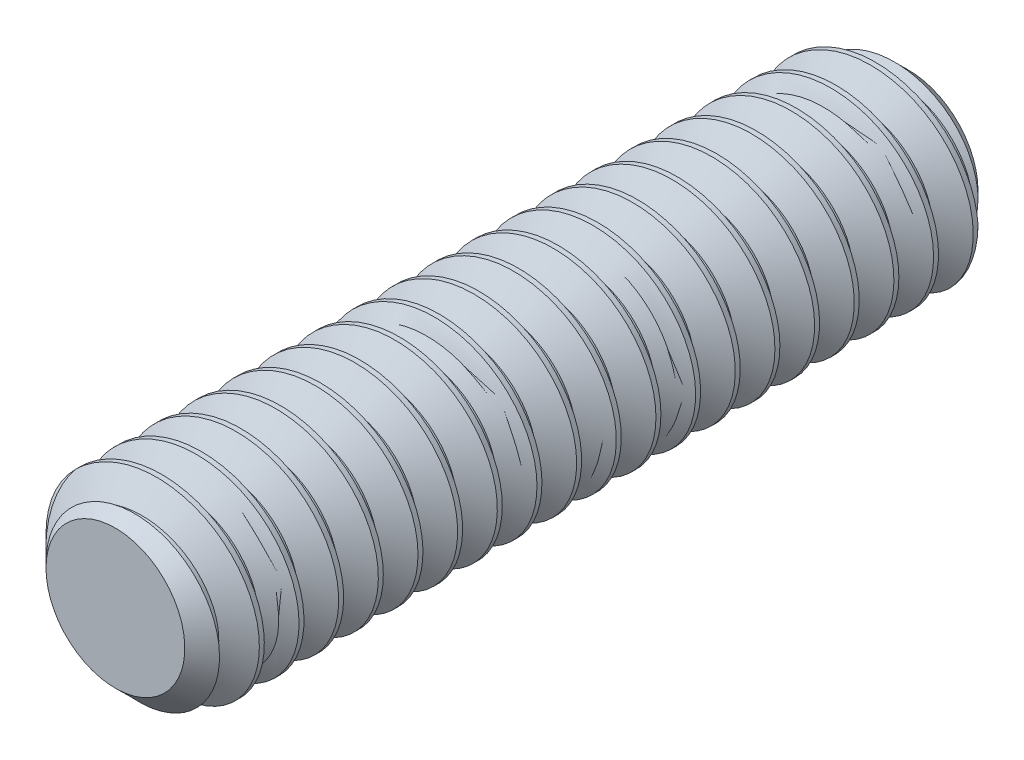
SolidWorks part; units mm, degrees
ref_plane "Front Plane" through (0, 0, 0) normal (0, 0, 1) x (1, 0, 0)
ref_plane "Top Plane" through (0, 0, 0) normal (0, 1, 0) x (1, 0, 0)
ref_plane "Right Plane" through (0, 0, 0) normal (1, 0, 0) x (0, 0, -1)
sketch "Sketch1" plane through (0, 0, 0) normal (1, 0, 0) x (0, 0, -1)
  line L1 (-12.7, 3.175) -> (12.7, 3.175)
  line L2 (-12.7, 3.175) -> (-12.7, 0)
  line L3 (-12.7, 0) -> (12.7, 0) construction
  line L4 (12.7, 3.175) -> (12.7, 0)
  point P4 (0, 0)
  point P5 (-11.43, 3.175)
  point P7 (9.525, 3.175)
  point P8 (9.525, -3.175)
  dimension "Thread Diameter" = 6.35
  dimension "Length" = 25.4
  dimension "Thread Pitch" = 1.27
  dimension "D1" = 3.175
sketch "Sketch2" plane through (0, 0, 0) normal (1, 0, 0) x (0, 0, -1)
  line L1 (-12.7, 0) -> (12.7, 0)
  line L2 (-12.7, 0) -> (-12.7, 3.175)
  line L3 (-12.7, 3.175) -> (12.7, 3.175)
  line L4 (12.7, 0) -> (12.7, 3.175)
revolve "Revolve1" add sketch "Sketch2" angle 360 about L1
chamfer "Chamfer1" distance 0.9525 angle 45 2 edges at (3.175, 0, -12.7) (3.175, 0, 12.7)
sketch "Drawing Reference 1" plane through (0, 0, 0) normal (1, 0, 0) x (0, 0, -1)
  line L0 (-12.7, 3.175) -> (12.7, 3.175) construction
  line L1 (-12.7, 3.175) -> (-12.7, 0) construction
  line L2 (12.7, 3.175) -> (12.7, 0) construction
  point P0 (-7.9375, 3.175)
  point P1 (7.9375, 3.175)
  dimension "D1" = 4.7625
  dimension "D2" = 4.7625
sketch "Sketch3" plane through (0, 0, -12.7) normal (0, 0, -1) x (-1, 0, 0)
  circle A0 centre (0, 0) radius 3.175 construction
  circle A1 centre (0, 0) radius 3.175
curve "Helix/Spiral1" pitch 1.27 height 26.67 radius 3.175 centre (0, 0, -12.7) axis (0, 0, 1) start towards (0, 1, 0) parameters "Helix Length"=26.67
sketch "Sketch4" plane through (0, 0, 0) normal (1, 0, 0) x (0, 0, -1)
  line L0 (12.6206, 3.3125) -> (13.2556, 2.2126) construction
  line L1 (13.2556, 2.2126) -> (13.8906, 3.3125) construction
  line L2 (13.8906, 3.3125) -> (12.6206, 3.3125) construction
  line L3 (12.6603, 3.2437) -> (13.8509, 3.2437)
  line L4 (13.8509, 3.2437) -> (13.335, 2.3501)
  line L5 (13.335, 2.3501) -> (13.1762, 2.3501)
  line L6 (13.1762, 2.3501) -> (12.6603, 3.2437)
  line L7 (13.2556, 2.3501) -> (13.2556, 2.2126) construction
  line L8 (12.7, 3.175) -> (13.8112, 3.175) construction
  line L9 (13.2556, 3.3125) -> (13.2556, 3.175) construction
  point P12 (13.2556, 3.2437)
  dimension "D1" = 1.27
  dimension "D2" = 0.1588
sweep "Cut-Sweep1" cut profiles "Sketch4" path "Helix/Spiral1"
sketch "Sketch5" plane through (0, 0, 12.7) normal (0, 0, 1) x (1, 0, 0)
  circle A0 centre (0, 0) radius 3.175 construction
  circle A1 centre (0, 0) radius 3.175 construction
equation "\"D1@Chamfer1\"=0.75*\"Thread Pitch@Sketch1\""
equation "\"D4@Helix/Spiral1\"=\"Thread Pitch@Sketch1\""
equation "\"D2@Sketch4\"=\"D1@Sketch4\"/8"
equation "\"D1@Sketch4\"=\"Thread Pitch@Sketch1\""
equation "\"D1@Drawing Reference 1\"=\"Thread Diameter@Sketch1\"*0.75"
equation "\"D2@Drawing Reference 1\" = \"D1@Drawing Reference 1\""
equation "\"D1@Sketch1\"=2.5*\"Thread Pitch@Sketch1\""
equation "\"Helix Length@Helix/Spiral1\"=\"Length@Sketch1\"+\"Thread Pitch@Sketch1\""
